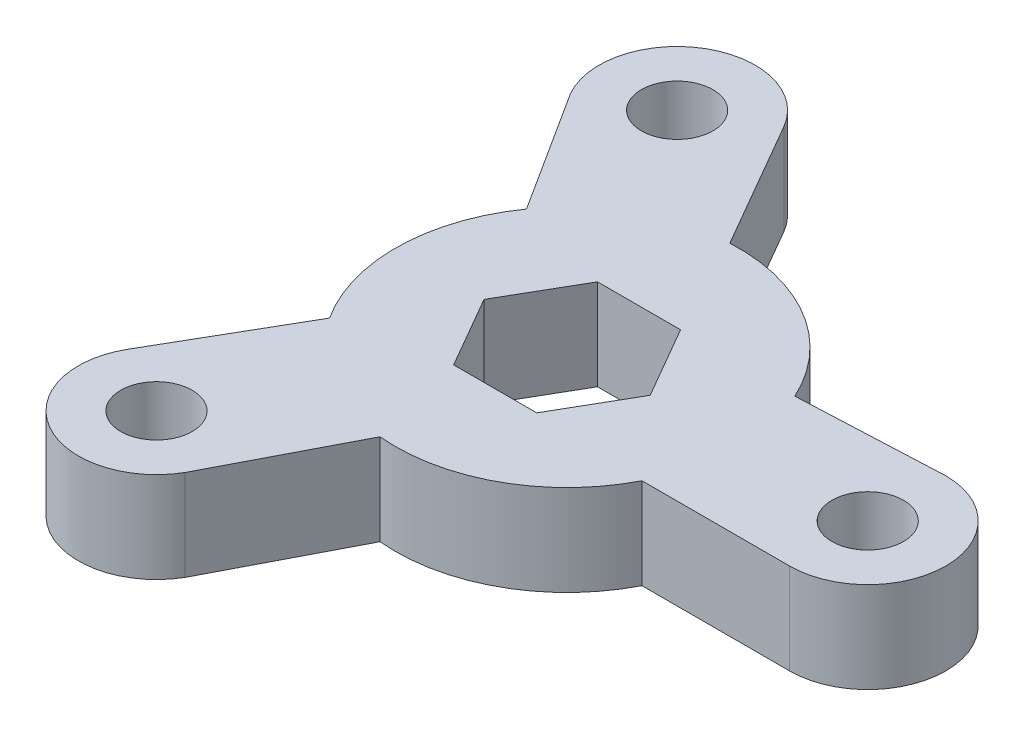
SolidWorks part; units mm, degrees
ref_plane "Front" through (0, 0, 0) normal (0, 0, 1) x (1, 0, 0)
ref_plane "Top" through (0, 0, 0) normal (0, 1, 0) x (1, 0, 0)
ref_plane "Right" through (0, 0, 0) normal (1, 0, 0) x (0, 0, -1)
sketch "Sketch1" plane through (0, 0, 0) normal (0, 1, 0) x (1, 0, 0)
  line L0 (2.5148, 0.2447) -> (13.0148, 0.2447)
  line L1 (2.5148, 0.2447) -> (-2.7352, 9.338)
  line L2 (2.5148, 0.2447) -> (-2.7352, -8.8486)
  line L3 (2.5148, 0.2447) -> (-2.7352, 9.338) construction
  line L10 (2.5148, 0.2447) -> (13.0148, 0.2447) construction
  line L11 (13.0148, -2.4841) -> (7.8583, -2.4841)
  line L12 (13.0148, 2.9736) -> (7.9691, 2.7447)
  line L13 (-5.0985, -7.4841) -> (-2.5203, -3.0185)
  line L14 (-0.372, -10.213) -> (1.9526, -5.7289)
  line L15 (-0.372, 10.7024) -> (2.2062, 6.2368)
  line L16 (-5.0985, 7.9736) -> (-2.3775, 3.7183)
  line L18 (5.4159, 0.2447) -> (3.9654, 2.7572)
  line L19 (3.9654, 2.7572) -> (1.0642, 2.7572)
  line L20 (1.0642, 2.7572) -> (-0.3864, 0.2447)
  line L21 (-0.3864, 0.2447) -> (1.0642, -2.2678)
  line L22 (1.0642, -2.2678) -> (3.9654, -2.2678)
  line L23 (3.9654, -2.2678) -> (5.4159, 0.2447)
  circle A0 centre (-2.7352, 9.338) radius 1.25
  circle A1 centre (13.0148, 0.2447) radius 1.25
  circle A2 centre (-2.7352, -8.8486) radius 1.25
  circle A3 centre (2.5148, 0.2447) radius 2.5125 construction
  arc A4 (-0.372, 10.7024) -> (-5.0985, 7.9736) centre (-2.7352, 9.338) ccw
  circle A5 centre (2.5148, 0.2447) radius 6
  arc A6 (13.0148, -2.4841) -> (13.0148, 2.9736) centre (13.0148, 0.2447) ccw
  arc A7 (-5.0985, -7.4841) -> (-0.372, -10.213) centre (-2.7352, -8.8486) ccw
  point P39 (2.5148, 0.2447)
  dimension "D1" = 3
  dimension "D2" = 120
  dimension "D3" = 3
extrude "Boss-Extrude1" add sketch "Sketch1" along normal blind 3.175 contours L0 A5 L1 L19 L18 | A5 L0 L23 L22 L2 | L1 A5 L2 L21 L20 | A5 L15 A4 L16 A0 | L11 A6 L12 A5 A1 | L13 A7 L14 A5 A2 region at (4.3914, 0, -3.4951) region at (4.3914, 0, 3.0056) region at (-1.2384, 0, -0.2447) region at (11.5994, 0, -0.1957) region at (-1.9851, 0, -8.1368) region at (-2.07, 0, 7.5983)
